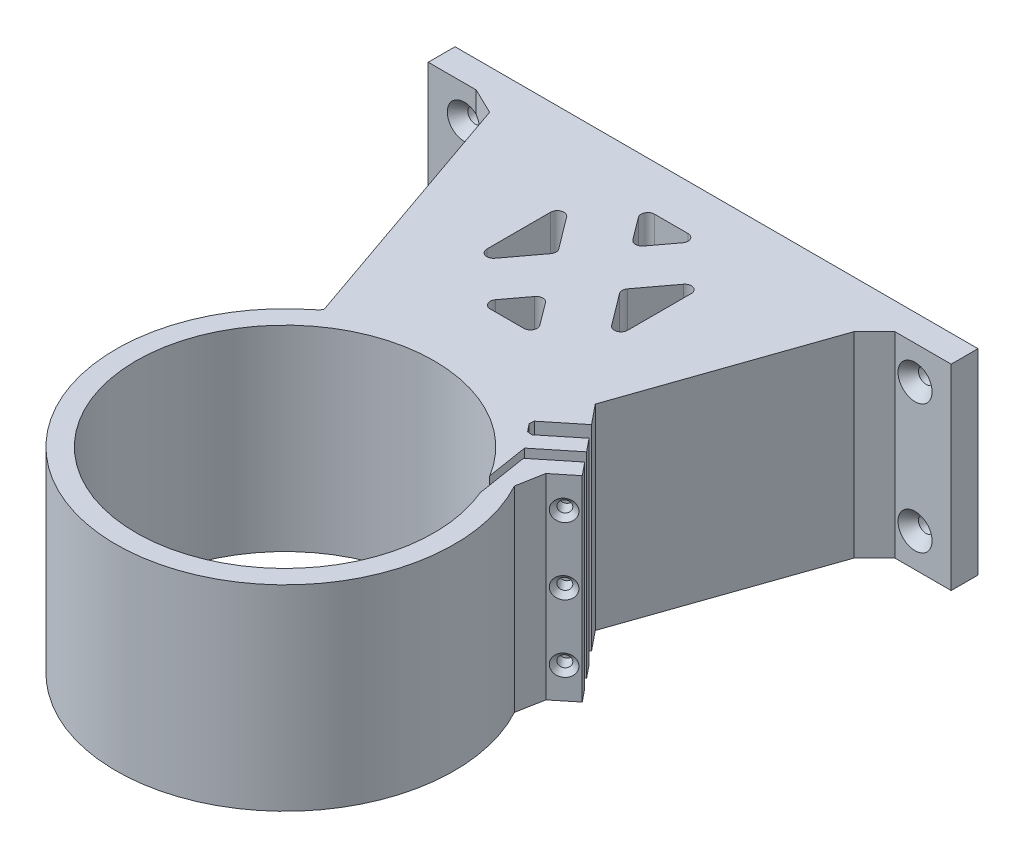
SolidWorks part; units mm, degrees
ref_plane "Front Plane" through (0, 0, 0) normal (0, 0, 1) x (1, 0, 0)
ref_plane "Top Plane" through (0, 0, 0) normal (0, 1, 0) x (1, 0, 0)
ref_plane "Right Plane" through (0, 0, 0) normal (1, 0, 0) x (0, 0, -1)
sketch "Sketch1" plane through (0, 0, 0) normal (0, 1, 0) x (1, 0, 0)
  line L0 (-27.5, 42.296) -> (-27.5, 82.296)
  line L5 (-27.5, 82.296) -> (-22.5, 82.296)
  line L6 (-22.5, 82.296) -> (-22.5, 72.296) construction
  line L7 (-22.5, 72.296) -> (22.5, 72.296) construction
  line L8 (22.5, 72.296) -> (22.5, 82.296) construction
  line L10 (32.5, 60.6712) -> (32.5, 38.6856) construction
  line L11 (36.0591, 35.3916) -> (38.0164, 23.0338)
  line L12 (38.5317, 32.5655) -> (40.952, 17.2839)
  line L14 (36.0591, 35.3916) -> (46.2731, 43.6628)
  line L15 (38.5317, 32.5655) -> (48.6345, 40.7467)
  line L16 (48.6345, 40.7467) -> (51.7812, 36.861)
  line L17 (51.7812, 36.861) -> (41.5671, 28.5898)
  line L18 (46.2731, 43.6628) -> (43.1265, 47.5485)
  line L19 (43.1265, 47.5485) -> (32.9125, 39.2774)
  line L20 (32.9125, 39.2774) -> (29.7659, 43.1631)
  line L21 (29.7659, 43.1631) -> (39.9799, 51.4343)
  line L22 (39.9799, 51.4343) -> (32.5, 60.6712)
  line L23 (22.5, 82.296) -> (32.5, 82.296)
  line L24 (32.5, 82.296) -> (32.5, 60.6712)
  line L30 (0, 44.45) -> (0, 72.296) construction
  line L31 (-22.5, 82.296) -> (22.5, 82.296)
  arc A1 (38.0164, 23.0338) -> (40.952, 17.2839) centre (0, 0) ccw
  arc A2 (36.0591, 35.3916) -> (32.5, 38.6856) centre (0, 0) ccw construction
  arc A3 (41.5671, 28.5898) -> (38.5317, 32.5655) centre (0, 0) ccw construction
  arc A4 (-27.5, 42.296) -> (41.5671, 28.5898) centre (0, 0) ccw
  point P9 (0, 72.296)
  point P13 (0, 70.296)
  dimension "D2" = 6
  dimension "D7" = 44.45
  dimension "D3" = 45
  dimension "D4" = 5
  dimension "D5" = 5
  dimension "D6" = 2
  dimension "D8" = 2
  dimension "D9" = 3
  dimension "D10" = 120
  dimension "D11" = 13
  dimension "D12" = 5
  dimension "D13" = 5
  dimension "D14" = 10
  dimension "D15" = 30
  dimension "D16" = 10
  dimension "D17" = 9
extrude "Boss-Extrude1" add sketch "Sketch1" along normal mid plane 58.5
chamfer "Chamfer1" distance 5 angle 45 1 edges at (41.5671, 0, -28.5898) first distance on face at (-1.3933, 0, 7.0211)
fillet "Fillet1" radius 10 1 edges at (-27.5, 0, -42.296)
chamfer "Chamfer2" distance 1 angle 45 2 edges at (29.7659, 0, -43.1631) (32.9125, 0, -39.2774)
hole_wizard "CSK for M3 Flat Head Machine Screw1" positions "Sketch2" profile "Sketch3" countersink size "M3" standard "ANSI Metric"
sketch "Sketch2" plane through (2.4799, 0, 3.0624) normal (0.6293, 0, 0.7771) x (0.7771, 0, -0.6293)
  line L0 (55.7375, 29.25) -> (63.4389, 29.25) construction
  point P0 (59.5882, 20)
  point P2 (59.5882, 0)
  point P4 (59.5882, -20)
  point P16 (59.5882, 29.25)
  dimension "D1" = 20
  dimension "D2" = 20
sketch "Sketch3" plane through (48.7886, 20, -34.4377) normal (0, 1, 0) x (0.7771, 0, -0.6293)
  line L0 (0, 0) -> (0, 16.0215)
  line L1 (0, 16.0215) -> (1.7, 15)
  line L2 (1.7, 15) -> (1.7, 1.45)
  line L3 (1.7, 1.45) -> (3.15, 0)
  line L5 (3.15, 0) -> (0, 0)
  line L6 (-1.7, 1.45) -> (-3.15, 0) construction
  line L10 (0, 16.0215) -> (-1.7, 15) construction
  line L11 (0, -6.35) -> (0, 107.95) construction
  dimension "Hole Dia." = 3.4
  dimension "Hole Depth" = 15
  dimension "Near C'Sink Dia." = 6.3
  dimension "Near C'Sink Angle" = 90
  dimension "Drill Angle" = 118
sketch "Sketch4" plane through (0, 29.25, 0) normal (0, 1, 0) x (1, 0, 0)
  line L0 (-27.473, 34.9433) -> (-60, 128.7)
  line L1 (-60, 128.7) -> (60, 128.7)
  line L2 (60, 128.7) -> (27.473, 34.9433)
  line L3 (60, 128.7) -> (78, 128.7)
  line L4 (78, 128.7) -> (78, 120.7)
  line L5 (78, 120.7) -> (57.2246, 120.7)
  line L6 (-60, 128.7) -> (-78, 128.7)
  line L7 (-78, 128.7) -> (-78, 120.7)
  line L8 (-78, 120.7) -> (-57.2246, 120.7)
  arc A0 (38.0164, 23.0338) -> (40.952, 17.2839) centre (0, 0) ccw construction
  arc A1 (-27.473, 34.9433) -> (27.473, 34.9433) centre (0, 0) cw
  point P8 (0, 128.7)
  line M8 (39.9799, 51.4343) -> (32.5, 60.6712)
  line M9 (32.5, 60.6712) -> (32.5, 82.296)
  line M10 (32.5, 82.296) -> (-27.5, 82.296)
  line M11 (-27.5, 82.296) -> (-27.5, 47.4126)
  arc M12 (-27.5, 47.4126) -> (-31.2965, 39.5693) centre (-37.5, 47.4126) cw
  dimension "D1" = 128.7
  dimension "D2" = 120
  dimension "D3" = 8
  dimension "D4" = 18
extrude "Boss-Extrude2" add sketch "Sketch4" against normal up to surface (58.5 mm away) contours L2 L1 L0 M12 M11 M10 M9 M8 | L7 L8 L0 L6 | L5 L4 L3 L2 region at (-68.2896, 29.25, -124.6046) region at (-1.1519, 29.25, -102.8434) region at (68.2896, 29.25, -124.6046) up to face at (24.2143, -29.25, -37.0477)
sketch "Sketch5" plane through (0, -29.25, 0) normal (0, -1, 0) x (1, 0, 0)
  line L13 (15, -110.7) -> (-15, -70.7) construction
  line L14 (9, -115.2) -> (-21, -75.2)
  line L15 (21, -106.2) -> (-9, -66.2)
  line L16 (-15, -110.7) -> (15, -70.7) construction
  line L17 (-21, -106.2) -> (9, -66.2)
  line L18 (-9, -115.2) -> (21, -75.2)
  line L19 (-9, -66.2) -> (9, -66.2)
  line L20 (21, -75.2) -> (21, -106.2)
  line L21 (9, -115.2) -> (-9, -115.2)
  line L22 (-21, -75.2) -> (-21, -106.2)
  line L25 (-57.2246, -120.7) -> (-78, -120.7) construction
  arc A0 (9, -115.2) -> (21, -106.2) centre (15, -110.7) ccw
  arc A1 (-9, -66.2) -> (-21, -75.2) centre (-15, -70.7) ccw
  arc A2 (-21, -106.2) -> (-9, -115.2) centre (-15, -110.7) ccw
  arc A3 (21, -75.2) -> (9, -66.2) centre (15, -70.7) ccw
  point P2 (0, -90.7)
  point P8 (0, -90.7)
  dimension "D1" = 15
  dimension "D2" = 20
  dimension "D3" = 30
  dimension "D4" = 15
  dimension "D5" = 30
extrude "Cut-Extrude1" cut sketch "Sketch5" against normal through all contours L21 L14 L18 | L14 L22 L17 | L19 L15 L17 | L20 L18 L15 region at (0, -29.25, -111.2) region at (17.125, -29.25, -90.7) region at (-17.125, -29.25, -90.7) region at (0, -29.25, -70.2)
fillet "Fillet2" radius 2 12 edges at (0, 0, -103.2) (-9, 0, -115.2) (9, 0, -115.2) (21, 0, -106.2) (21, 0, -75.2) (9.375, 0, -90.7) (0, 0, -78.2) (9, 0, -66.2) (-9, 0, -66.2) (-21, 0, -106.2) (-9.375, 0, -90.7) (-21, 0, -75.2)
hole_wizard "CSK for #8 Flat Head Machine Screw1" positions "Sketch6" profile "Sketch7" countersink size "#8" standard "ANSI Inch" end condition through all
sketch "Sketch6" plane through (0, 0, -120.7) normal (0, 0, 1) x (1, 0, 0)
  line L0 (-57.2246, -29.25) -> (-57.2246, 29.25) construction
  line L1 (-78, 29.25) -> (-57.2246, 29.25) construction
  line L2 (-57.2246, -29.25) -> (-78, -29.25) construction
  line L4 (57.2246, -29.25) -> (57.2246, 29.25) construction
  point P0 (-67.2246, 19.25)
  point P2 (-67.2246, -19.25)
  point P4 (67.2246, 19.25)
  point P6 (67.2246, -19.25)
  dimension "D1" = 10
  dimension "D2" = 10
  dimension "D3" = 10
  dimension "D4" = 10
sketch "Sketch7" plane through (-67.2246, 19.25, -120.7) normal (1, 0, 0) x (0, -1, 0)
  line L0 (0, 0) -> (0, 8)
  line L1 (0, 8) -> (2.2479, 8)
  line L2 (2.2479, 8) -> (2.2479, 3.2645)
  line L3 (2.2479, 3.2645) -> (5.0857, 0)
  line L5 (5.0857, 0) -> (0, 0)
  line L6 (-2.2479, 3.2645) -> (-5.0857, 0) construction
  line L11 (0, -6.35) -> (0, 107.95) construction
  dimension "Thru Hole Dia." = 4.4958
  dimension "Thru Hole Depth" = 8
  dimension "Near C'Sink Dia." = 10.1714
  dimension "Near C'Sink Angle" = 82
chamfer "Chamfer3" distance 4 angle 45 2 edges at (57.2246, 0, -120.7) (-57.2246, 0, -120.7) first distance on face at (72.3103, 19.25, -120.7) first distance on face at (-43.4372, 0, -80.9589)
